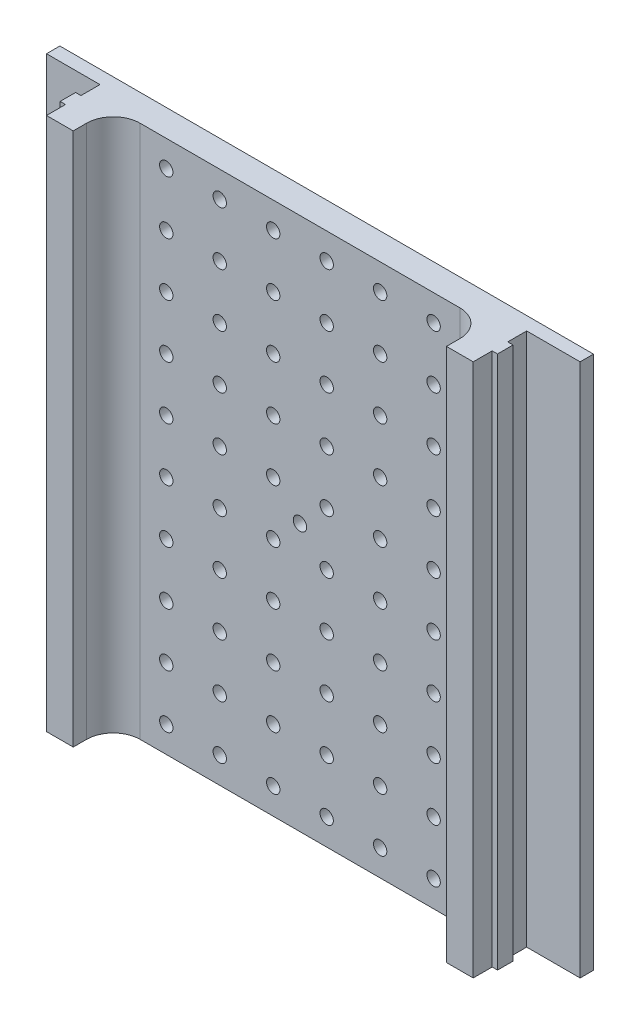
SolidWorks part; units mm, degrees
ref_plane "Front Plane" through (0, 0, 0) normal (0, 0, 1) x (1, 0, 0)
ref_plane "Top Plane" through (0, 0, 0) normal (0, 1, 0) x (1, 0, 0)
ref_plane "Right Plane" through (0, 0, 0) normal (1, 0, 0) x (0, 0, -1)
sketch "Sketch1" plane through (0, 0, 0) normal (0, 0, 1) x (1, 0, 0)
  line L1 (-49.9, -49.9) -> (49.9, -49.9)
  line L2 (-49.9, -49.9) -> (-49.9, 49.9)
  line L3 (-49.9, 49.9) -> (49.9, 49.9)
  line L4 (49.9, -49.9) -> (49.9, 49.9)
  line L5 (-49.9, -49.9) -> (49.9, 49.9) construction
  line L6 (-49.9, 49.9) -> (49.9, -49.9) construction
  point P0 (0, 0)
  dimension "D1" = 99.8
  dimension "D2" = 99.8
extrude "Main" add sketch "Sketch1" along normal blind 12.5
sketch "Sketch2" plane through (0, 49.9, 0) normal (0, 1, 0) x (1, 0, 0)
  line L0 (-39.9, -8.95) -> (-39.9, -12.5)
  line L1 (49.9, -12.5) -> (-49.9, -12.5) construction
  line L8 (-39.9, -2.5) -> (-49.9, -2.5)
  line L9 (-39.9, -2.5) -> (-39.9, -6.05)
  line L10 (-39.9, -6.05) -> (-40.9, -6.05)
  line L11 (-40.9, -6.05) -> (-40.9, -8.95)
  line L12 (-40.9, -8.95) -> (-39.9, -8.95)
  line L15 (-49.9, -12.5) -> (-49.9, 0) construction
  line L16 (-49.9, -2.5) -> (-49.9, -12.5)
  line L17 (-49.9, -12.5) -> (-39.9, -12.5)
  dimension "D1" = 10
  dimension "D2" = 10
  dimension "D3" = 1
  dimension "D4" = 2.9
extrude "Cut-Extrude1" cut sketch "Sketch2" against normal through all and the other way through all
mirror "Mirror1" about plane through (0, 0, 0) normal (1, 0, 0) of "Cut-Extrude1"
sketch "Sketch3" plane through (0, 49.9, 0) normal (0, 1, 0) x (1, 0, 0)
  line L0 (39.9, -12.5) -> (-39.9, -12.5) construction
  line L1 (-34.9, -12.5) -> (34.9, -12.5)
  line L2 (-34.9, -12.5) -> (-34.9, -5)
  line L3 (-34.9, -5) -> (34.9, -5)
  line L4 (34.9, -12.5) -> (34.9, -5)
  line L5 (-39.9, -2.5) -> (-39.9, -6.05) construction
  line L6 (39.9, -2.5) -> (39.9, -6.05) construction
  line L10 (-49.9, 0) -> (49.9, 0) construction
  point P10 (39.9, -4.275)
  dimension "D1" = 5
  dimension "D2" = 5
  dimension "D3" = 5
extrude "Cut-Extrude2" cut sketch "Sketch3" against normal through all
fillet "Fillet1" radius 5 2 edges at (-34.9, 0, 5) (34.9, 0, 5)
sketch "Sketch4" plane through (0, 0, 5) normal (0, 0, 1) x (1, 0, 0)
  circle A0 centre (25, -45) radius 1.25
  dimension "D1" = 2.5
  dimension "D2" = 45
  dimension "D3" = 25
extrude "FixHole" cut sketch "Sketch4" against normal through all
pattern_linear "LPattern1" count 6 spacing 10 along (-1, 0, 0) count 10 spacing 10 along (0, 1, 0) of "FixHole"
sketch "Sketch6" plane through (0, 0, 5) normal (0, 0, 1) x (1, 0, 0)
  circle A0 centre (0, 0) radius 1.25
  point P2 (0, 0)
  dimension "D1" = 2.5
extrude "Cut-Extrude4" cut sketch "Sketch6" against normal through all
